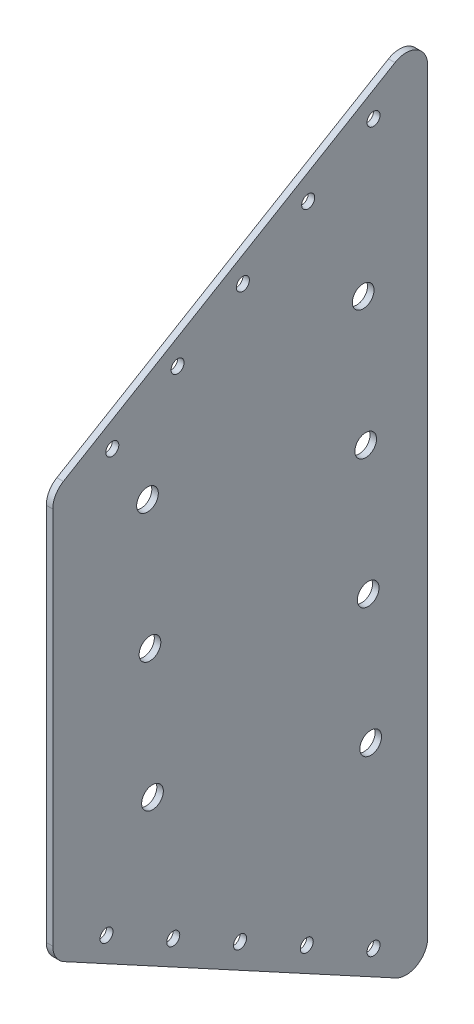
SolidWorks part; units mm, degrees
ref_plane "Front Plane" through (0, 0, 0) normal (0, 0, 1) x (1, 0, 0)
ref_plane "Top Plane" through (0, 0, 0) normal (0, 1, 0) x (1, 0, 0)
ref_plane "Right Plane" through (0, 0, 0) normal (1, 0, 0) x (0, 0, -1)
sketch "Sketch1" plane through (0, 0, 0) normal (1, 0, 0) x (0, 0, -1)
  line L0 (459.131, 411.7337) -> (459.131, 597.8495)
  line L6 (459.131, 597.8495) -> (631.9465, 700.452)
  line L7 (631.9465, 700.452) -> (631.9465, 317.9454)
  line L8 (631.9465, 317.9454) -> (459.131, 411.7337)
extrude "Boss-Extrude1" add sketch "Sketch1" along normal blind 3
sketch "Sketch3" plane through (3, 0, 0) normal (1, 0, 0) x (0, 0, -1)
  line L2 (631.9465, 700.452) -> (459.131, 597.8495) construction
  line L3 (459.131, 411.7337) -> (631.9465, 317.9454) construction
  circle A0 centre (516.6602, 620.3756) radius 3
  circle A1 centre (546.7556, 638.2436) radius 3
  circle A2 centre (576.851, 656.1116) radius 3
  circle A3 centre (514.6611, 392.9749) radius 3
  circle A4 centre (545.4229, 376.2802) radius 3
  circle A5 centre (576.1847, 359.5855) radius 3
  circle A6 centre (486.5648, 602.5076) radius 3
  circle A7 centre (606.9465, 673.9796) radius 3
  circle A8 centre (483.8993, 409.6695) radius 3
  circle A9 centre (606.9465, 342.8908) radius 3
  dimension "D4" = 6
  dimension "D5" = 6
  dimension "D6" = 6
  dimension "D12" = 6
  dimension "D13" = 6
  dimension "D14" = 6
  dimension "D17" = 6
  dimension "D18" = 6
  dimension "D19" = 6
  dimension "D20" = 6
  dimension "D3" = 10
  dimension "D7" = 35
  dimension "D8" = 35
  dimension "D9" = 10
  dimension "D10" = 10
  dimension "D11" = 10
  dimension "D15" = 35
  dimension "D16" = 35
  dimension "D21" = 10
  dimension "D22" = 10
  dimension "D23" = 35
  dimension "D24" = 35
  dimension "D25" = 10
  dimension "D26" = 10
  dimension "D27" = 10
  dimension "D28" = 10
  dimension "D29" = 35
  dimension "D30" = 35
  dimension "D31" = 25
  dimension "D32" = 25
extrude "Cut-Extrude1" cut sketch "Sketch3" against normal up to next
sketch "Sketch4" plane through (3, 0, 0) normal (1, 0, 0) x (0, 0, -1)
  circle A0 centre (602.1866, 605.5563) radius 5 construction
  circle A1 centre (603.3438, 545.5674) radius 5 construction
  circle A2 centre (604.5009, 485.5786) radius 5 construction
  circle A3 centre (605.6581, 425.5898) radius 5 construction
  circle A4 centre (502.7743, 574.1246) radius 5 construction
  circle A5 centre (503.9315, 514.1358) radius 5 construction
  circle A6 centre (505.0886, 454.1469) radius 5 construction
  circle A7 centre (602.1866, 605.5563) radius 5
  circle A8 centre (603.3438, 545.5674) radius 5
  circle A9 centre (604.5009, 485.5786) radius 5
  circle A10 centre (605.6581, 425.5898) radius 5
  circle A11 centre (502.7743, 574.1246) radius 5
  circle A12 centre (503.9315, 514.1358) radius 5
  circle A13 centre (505.0886, 454.1469) radius 5
extrude "Cut-Extrude2" cut sketch "Sketch4" against normal up to next
fillet "Fillet1" radius 10 4 edges at (1.5, 597.8495, -459.131) (1.5, 411.7337, -459.131) (1.5, 317.9454, -631.9465) (1.5, 700.452, -631.9465)
